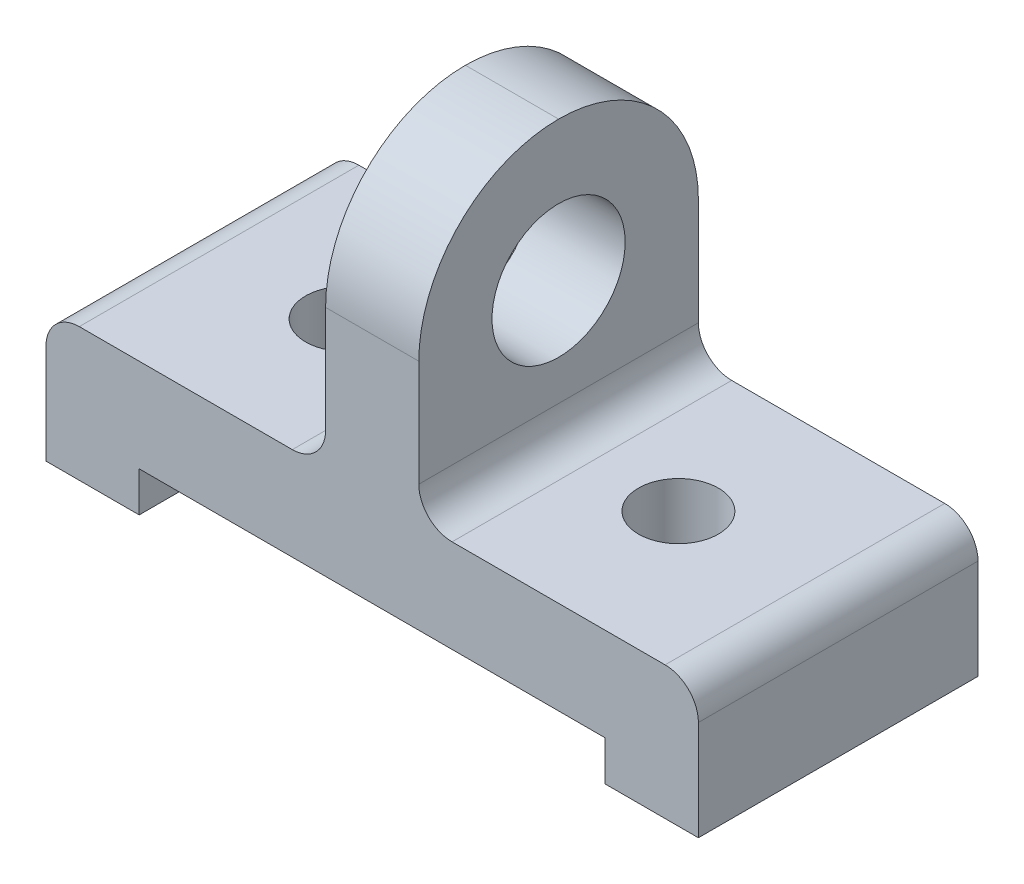
SolidWorks part; units mm, degrees
ref_plane "Front Plane" through (0, 0, 0) normal (0, 0, 1) x (1, 0, 0)
ref_plane "Top Plane" through (0, 0, 0) normal (0, 1, 0) x (1, 0, 0)
ref_plane "Right Plane" through (0, 0, 0) normal (1, 0, 0) x (0, 0, -1)
sketch "Sketch1" plane through (0, 0, 0) normal (0, 1, 0) x (1, 0, 0)
  line L1 (0, 0) -> (248.92, 0)
  line L2 (0, 0) -> (0, -106.68)
  line L3 (0, -106.68) -> (248.92, -106.68)
  line L4 (248.92, 0) -> (248.92, -106.68)
  dimension "D1" = 248.92
  dimension "D2" = 106.68
extrude "Boss-Extrude1" add sketch "Sketch1" along normal blind 50.8
sketch "Sketch2" plane through (0, 0, 0) normal (0, -1, 0) x (1, 0, 0)
  line L0 (0, 106.68) -> (248.92, 106.68) construction
  line L1 (35.56, 106.68) -> (213.36, 106.68)
  line L2 (35.56, 106.68) -> (35.56, 0)
  line L3 (35.56, 0) -> (213.36, 0)
  line L4 (213.36, 106.68) -> (213.36, 0)
  line L5 (248.92, 0) -> (0, 0) construction
  line L6 (0, 0) -> (0, 106.68) construction
  line L7 (248.92, 106.68) -> (248.92, 0) construction
  dimension "D1" = 35.56
  dimension "D2" = 35.56
extrude "Cut-Extrude1" cut sketch "Sketch2" against normal blind 15.24
sketch "Sketch3" plane through (0, 50.8, 0) normal (0, 1, 0) x (1, 0, 0)
  line L0 (0, -53.34) -> (248.92, -53.34) construction
  line L1 (0, 0) -> (0, -106.68) construction
  line L2 (248.92, -106.68) -> (248.92, 0) construction
  line L3 (248.92, 0) -> (0, 0) construction
  line L4 (106.68, 0) -> (142.24, 0)
  line L5 (106.68, 0) -> (106.68, -106.68)
  line L6 (106.68, -106.68) -> (142.24, -106.68)
  line L7 (142.24, 0) -> (142.24, -106.68)
  line L8 (0, -106.68) -> (248.92, -106.68) construction
  line L9 (106.68, 0) -> (142.24, -106.68) construction
  line L10 (106.68, -106.68) -> (142.24, 0) construction
  circle A0 centre (60.96, -53.34) radius 15.24
  circle A1 centre (187.96, -53.34) radius 15.24
  point P10 (124.46, -53.34)
  point P19 (124.46, -53.34)
  dimension "D1" = 60.96
  dimension "D2" = 30.48
  dimension "D3" = 60.96
  dimension "D4" = 30.48
  dimension "D5" = 35.56
  dimension "D6" = 53.34
extrude "Cut-Extrude3" cut sketch "Sketch3" against normal blind 35.56 contours A0 | A1
extrude "Boss-Extrude2" add sketch "Sketch3<4>" along normal blind 106.68 contours L7 L6 L5 L4
sketch "Sketch3<4>" plane through (0, 50.8, 0) normal (0, 1, 0) x (1, 0, 0) same geometry as "Sketch3"
sketch "Sketch4" plane through (142.24, 0, 0) normal (1, 0, 0) x (0, 0, -1)
  line L0 (-106.68, 104.14) -> (0, 104.14) construction
  line L1 (-106.68, 157.48) -> (-106.68, 50.8) construction
  line L2 (0, 157.48) -> (0, 50.8) construction
  line L3 (0, 50.8) -> (-106.68, 50.8) construction
  circle A0 centre (-53.34, 104.14) radius 25.4
  dimension "D2" = 50.8
  dimension "D1" = 53.34
extrude "Cut-Extrude4" cut sketch "Sketch4" against normal blind 35.56
fillet "Fillet1" radius 53.34 2 edges at (124.46, 157.48, 106.68) (124.46, 157.48, 0)
fillet "Fillet2" radius 12.7 2 edges at (248.92, 50.8, 53.34) (0, 50.8, 53.34)
fillet "Fillet3" radius 12.7 2 edges at (106.68, 50.8, 53.34) (142.24, 50.8, 53.34)
